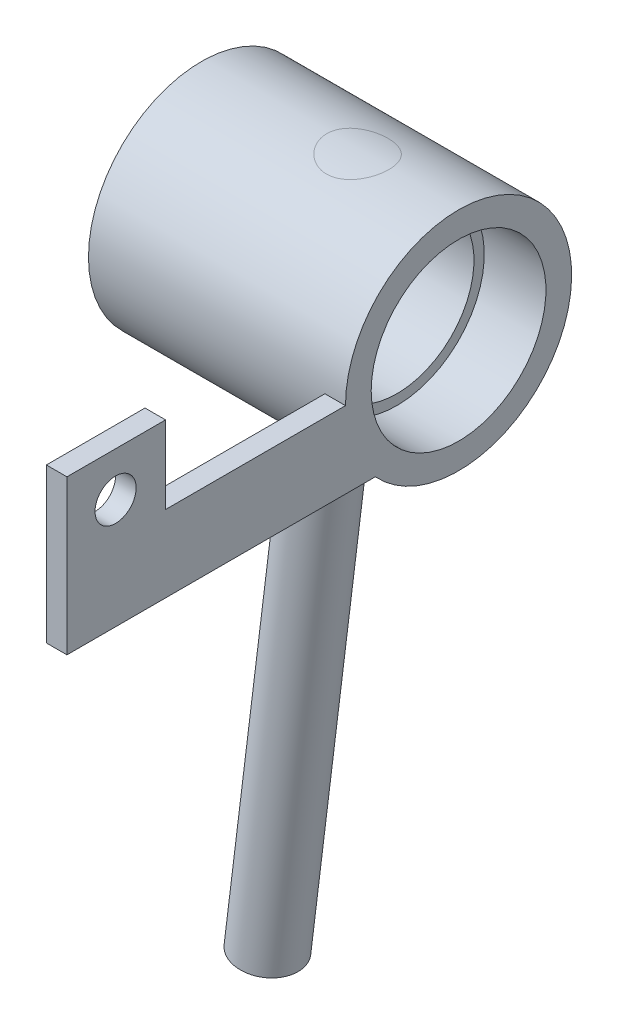
SolidWorks part; units mm, degrees
ref_plane "Front Plane" through (0, 0, 0) normal (0, 0, 1) x (1, 0, 0)
ref_plane "Top Plane" through (0, 0, 0) normal (0, 1, 0) x (1, 0, 0)
ref_plane "Right Plane" through (0, 0, 0) normal (1, 0, 0) x (0, 0, -1)
sketch "Sketch1" plane through (0, 0, 0) normal (0, 0, 1) x (1, 0, 0)
  line L0 (-25, 22) -> (-25, 17)
  line L1 (-25, 17) -> (-13, 17)
  line L2 (-13, 17) -> (-13, 15)
  line L3 (-13, 15) -> (13, 15)
  line L4 (13, 15) -> (13, 17)
  line L5 (13, 17) -> (25, 17)
  line L6 (25, 17) -> (25, 22)
  line L7 (-25, 22) -> (25, 22)
  line L8 (-45.7661, 0) -> (25, 0) construction
  line L9 (55, 0) -> (-55, 0) construction
  point P4 (0, 22)
  point P9 (0, 15)
  dimension "D1" = 50
  dimension "D2" = 5
  dimension "D3" = 2
  dimension "D4" = 12
  dimension "D5" = 22
revolve "Revolve1" add sketch "Sketch1" angle 360 about L8
sketch "Sketch6" plane through (0, 0, 0) normal (1, 0, 0) x (0, 0, -1)
  line L0 (-17.9634, -22) -> (15.1324, -22) construction
  circle A0 centre (0, 0) radius 22 construction
ref_plane "Plane2" through (-2.6611, -21.6733, 0) normal (0.1219, 0.9925, 0) x (0, 0, -1)
sketch "Sketch7" plane through (-2.6611, -21.6733, 0) normal (0.1219, 0.9925, 0) x (0, 0, -1)
  line L0 (-200017.9634, -2.6811) -> (200015.1324, -2.6811) construction
  line L2 (0, 55) -> (0, -55) construction
  circle A0 centre (0, -2.6811) radius 6
  dimension "D1" = 12
split line "Split Line2"
sketch3d "3DSketch1"
  spline S0 degree 3 poles (11.4476, 22, 0.4001) (11.4476, 22, -0.4001) (11.4063, 21.9891, -0.7927) (11.2456, 21.9477, -1.5639) (11.124, 21.9167, -1.9465) (10.8108, 21.8404, -2.6701) (10.6199, 21.7952, -3.0126) (10.2834, 21.7207, -3.4982) (10.1623, 21.6946, -3.6559) (9.9077, 21.6419, -3.9561) (9.7739, 21.6152, -4.0991) (9.3535, 21.535, -4.508) (9.047, 21.4813, -4.7544) (8.3859, 21.3804, -5.1894) (8.0395, 21.3344, -5.3728) (7.4963, 21.2759, -5.5986) (7.3113, 21.2581, -5.6655) (6.933, 21.2266, -5.7823) (6.7391, 21.2129, -5.8322) (6.1576, 21.1796, -5.9524) (5.7664, 21.1674, -5.9949) (4.977, 21.1648, -6.0042) (4.5752, 21.1747, -5.9696) (3.7998, 21.2152, -5.8241) (3.4225, 21.2456, -5.7139) (2.8725, 21.3038, -5.4911) (2.6916, 21.3254, -5.4069) (2.3434, 21.3712, -5.223) (2.1749, 21.3955, -5.1228) (1.8492, 21.4462, -4.9063) (1.6918, 21.4726, -4.79) (1.3882, 21.5266, -4.541) (1.2413, 21.5544, -4.4075) (0.8244, 21.6373, -3.9886) (0.5778, 21.6916, -3.6854) (0.1453, 21.7926, -3.0317) (-0.0415, 21.8395, -2.6776) (-0.3386, 21.9165, -1.9494) (-0.4513, 21.9472, -1.5729) (-0.5658, 21.9786, -0.989) (-0.5948, 21.9867, -0.7905) (-0.633, 21.9973, -0.3959) (-0.6425, 22, -0.1987) (-0.6426, 22, 0.3925) (-0.6049, 21.9894, 0.788) (-0.4522, 21.9474, 1.5698) (-0.3395, 21.9167, 1.9468) (-0.043, 21.8399, 2.6744) (0.1434, 21.7931, 3.0283) (0.5762, 21.692, 3.6833) (0.8224, 21.6377, 3.9863) (1.2376, 21.5551, 4.4041) (1.3846, 21.5273, 4.5378) (1.6889, 21.4731, 4.7877) (1.8463, 21.4467, 4.9042) (2.3345, 21.3707, 5.2291) (2.6808, 21.3242, 5.413) (3.418, 21.246, 5.7126) (3.7964, 21.2155, 5.8231) (4.3768, 21.1851, 5.9325) (4.5724, 21.1775, 5.9595) (4.9684, 21.1677, 5.9942) (5.1689, 21.1655, 6.0018) (5.7637, 21.1674, 5.9953) (6.1556, 21.1795, 5.9527) (6.7369, 21.2128, 5.8327) (6.9306, 21.2264, 5.783) (7.3096, 21.2579, 5.6661) (7.495, 21.2757, 5.599) (8.0392, 21.3344, 5.373) (8.3861, 21.3804, 5.1893) (9.048, 21.4814, 4.7537) (9.3536, 21.535, 4.5079) (9.7735, 21.6151, 4.0995) (9.9072, 21.6418, 3.9566) (10.1615, 21.6945, 3.6569) (10.2827, 21.7206, 3.4992) (10.6195, 21.7951, 3.0134) (10.8099, 21.8402, 2.6716) (11.1221, 21.9163, 1.9515) (11.2445, 21.9474, 1.5686) (11.4063, 21.9891, 0.7938) (11.4476, 22, 0.4001) (11.4476, 22, -0.4001) (11.4063, 21.9891, -0.7927) knots -0.03125 -0.03125 0 0 0.03125 0.03125 0.0625 0.0625 0.09375 0.09375 0.109375 0.109375 0.125 0.125 0.15625 0.15625 0.1875 0.1875 0.203125 0.203125 0.21875 0.21875 0.25 0.25 0.28125 0.28125 0.3125 0.3125 0.328125 0.328125 0.34375 0.34375 0.359375 0.359375 0.375 0.375 0.40625 0.40625 0.4375 0.4375 0.46875 0.46875 0.484375 0.484375 0.5 0.5 0.53125 0.53125 0.5625 0.5625 0.59375 0.59375 0.625 0.625 0.640625 0.640625 0.65625 0.65625 0.6875 0.6875 0.71875 0.71875 0.734375 0.734375 0.75 0.75 0.78125 0.78125 0.796875 0.796875 0.8125 0.8125 0.84375 0.84375 0.875 0.875 0.890625 0.890625 0.90625 0.90625 0.9375 0.9375 0.96875 0.96875 1 1 1.03125 1.03125 1.0625 only from (11.4476, 22, 0) to (11.4476, 22, 0) construction
  spline S1 degree 3 poles (11.4476, 22, 0.4001) (11.4476, 22, -0.4001) (11.4063, 21.9891, -0.7927) (11.2456, 21.9477, -1.5639) (11.124, 21.9167, -1.9465) (10.8108, 21.8404, -2.6701) (10.6199, 21.7952, -3.0126) (10.2834, 21.7207, -3.4982) (10.1623, 21.6946, -3.6559) (9.9077, 21.6419, -3.9561) (9.7739, 21.6152, -4.0991) (9.3535, 21.535, -4.508) (9.047, 21.4813, -4.7544) (8.3859, 21.3804, -5.1894) (8.0395, 21.3344, -5.3728) (7.4963, 21.2759, -5.5986) (7.3113, 21.2581, -5.6655) (6.933, 21.2266, -5.7823) (6.7391, 21.2129, -5.8322) (6.1576, 21.1796, -5.9524) (5.7664, 21.1674, -5.9949) (4.977, 21.1648, -6.0042) (4.5752, 21.1747, -5.9696) (3.7998, 21.2152, -5.8241) (3.4225, 21.2456, -5.7139) (2.8725, 21.3038, -5.4911) (2.6916, 21.3254, -5.4069) (2.3434, 21.3712, -5.223) (2.1749, 21.3955, -5.1228) (1.8492, 21.4462, -4.9063) (1.6918, 21.4726, -4.79) (1.3882, 21.5266, -4.541) (1.2413, 21.5544, -4.4075) (0.8244, 21.6373, -3.9886) (0.5778, 21.6916, -3.6854) (0.1453, 21.7926, -3.0317) (-0.0415, 21.8395, -2.6776) (-0.3386, 21.9165, -1.9494) (-0.4513, 21.9472, -1.5729) (-0.5658, 21.9786, -0.989) (-0.5948, 21.9867, -0.7905) (-0.633, 21.9973, -0.3959) (-0.6425, 22, -0.1987) (-0.6426, 22, 0.3925) (-0.6049, 21.9894, 0.788) (-0.4522, 21.9474, 1.5698) (-0.3395, 21.9167, 1.9468) (-0.043, 21.8399, 2.6744) (0.1434, 21.7931, 3.0283) (0.5762, 21.692, 3.6833) (0.8224, 21.6377, 3.9863) (1.2376, 21.5551, 4.4041) (1.3846, 21.5273, 4.5378) (1.6889, 21.4731, 4.7877) (1.8463, 21.4467, 4.9042) (2.3345, 21.3707, 5.2291) (2.6808, 21.3242, 5.413) (3.418, 21.246, 5.7126) (3.7964, 21.2155, 5.8231) (4.3768, 21.1851, 5.9325) (4.5724, 21.1775, 5.9595) (4.9684, 21.1677, 5.9942) (5.1689, 21.1655, 6.0018) (5.7637, 21.1674, 5.9953) (6.1556, 21.1795, 5.9527) (6.7369, 21.2128, 5.8327) (6.9306, 21.2264, 5.783) (7.3096, 21.2579, 5.6661) (7.495, 21.2757, 5.599) (8.0392, 21.3344, 5.373) (8.3861, 21.3804, 5.1893) (9.048, 21.4814, 4.7537) (9.3536, 21.535, 4.5079) (9.7735, 21.6151, 4.0995) (9.9072, 21.6418, 3.9566) (10.1615, 21.6945, 3.6569) (10.2827, 21.7206, 3.4992) (10.6195, 21.7951, 3.0134) (10.8099, 21.8402, 2.6716) (11.1221, 21.9163, 1.9515) (11.2445, 21.9474, 1.5686) (11.4063, 21.9891, 0.7938) (11.4476, 22, 0.4001) (11.4476, 22, -0.4001) (11.4063, 21.9891, -0.7927) knots -0.03125 -0.03125 0 0 0.03125 0.03125 0.0625 0.0625 0.09375 0.09375 0.109375 0.109375 0.125 0.125 0.15625 0.15625 0.1875 0.1875 0.203125 0.203125 0.21875 0.21875 0.25 0.25 0.28125 0.28125 0.3125 0.3125 0.328125 0.328125 0.34375 0.34375 0.359375 0.359375 0.375 0.375 0.40625 0.40625 0.4375 0.4375 0.46875 0.46875 0.484375 0.484375 0.5 0.5 0.53125 0.53125 0.5625 0.5625 0.59375 0.59375 0.625 0.625 0.640625 0.640625 0.65625 0.65625 0.6875 0.6875 0.71875 0.71875 0.734375 0.734375 0.75 0.75 0.78125 0.78125 0.796875 0.796875 0.8125 0.8125 0.84375 0.84375 0.875 0.875 0.890625 0.890625 0.90625 0.90625 0.9375 0.9375 0.96875 0.96875 1 1 1.03125 1.03125 1.0625 only from (11.4476, 22, 0) to (11.4476, 22, 0)
sketch3d "3DSketch2"
  spline S0 degree 3 poles (6.0451, -22, -0.3998) (6.0451, -22, 0.3998) (6.0065, -21.9891, 0.7928) (5.8933, -21.958, 1.3724) (5.8463, -21.9452, 1.5639) (5.733, -21.9148, 1.9437) (5.6666, -21.8972, 2.1321) (5.4429, -21.8392, 2.68) (5.2603, -21.7934, 3.0263) (4.8277, -21.6923, 3.6815) (4.576, -21.6369, 3.9908) (4.0249, -21.5273, 4.5446) (3.7233, -21.4727, 4.793) (3.0653, -21.3702, 5.231) (2.7159, -21.3236, 5.4154) (2.1711, -21.2658, 5.6367) (1.9855, -21.2484, 5.7016) (1.6063, -21.2182, 5.8131) (1.4116, -21.2053, 5.8599) (0.8265, -21.1747, 5.9699) (0.4338, -21.1649, 6.0038) (-0.3568, -21.1673, 5.9955) (-0.7573, -21.1797, 5.952) (-1.5298, -21.224, 5.7922) (-1.906, -21.2557, 5.6764) (-2.6383, -21.3345, 5.3725) (-2.9874, -21.381, 5.1868) (-3.4775, -21.4558, 4.8643) (-3.6358, -21.4817, 4.7491) (-3.9422, -21.5345, 4.5033) (-4.0909, -21.5617, 4.3719) (-4.5145, -21.6425, 3.9598) (-4.767, -21.6955, 3.662) (-5.1016, -21.7696, 3.18) (-5.2057, -21.7933, 3.0134) (-5.3984, -21.8383, 2.6679) (-5.4865, -21.8595, 2.4894) (-5.7211, -21.9167, 1.9474) (-5.8404, -21.9471, 1.5737) (-5.9622, -21.9784, 0.994) (-5.9933, -21.9865, 0.7963) (-6.0346, -21.9973, 0.4001) (-6.0449, -22, 0.2025) (-6.0454, -22.0001, -0.3891) (-6.0057, -21.9896, -0.7818) (-5.8436, -21.9479, -1.5637) (-5.7238, -21.9173, -1.9398) (-5.4124, -21.8414, -2.6619) (-5.218, -21.7954, -3.0115) (-4.7706, -21.6963, -3.6576) (-4.5178, -21.6432, -3.9561) (-4.0951, -21.5624, -4.3681) (-3.9463, -21.5353, -4.4998) (-3.6396, -21.4823, -4.7463) (-3.4813, -21.4564, -4.8616) (-2.9913, -21.3815, -5.1845) (-2.645, -21.3353, -5.3692) (-1.9106, -21.2561, -5.6749) (-1.5344, -21.2243, -5.7908) (-0.9571, -21.1911, -5.9108) (-0.7624, -21.1824, -5.9418) (-0.3686, -21.1703, -5.985) (-0.1682, -21.1668, -5.9972) (0.4278, -21.1648, -6.0043) (0.8203, -21.1745, -5.9704) (1.5955, -21.2147, -5.8259) (1.9817, -21.2458, -5.7132) (2.711, -21.323, -5.4179) (3.0577, -21.3692, -5.2353) (3.5509, -21.4458, -4.9081) (3.7108, -21.4726, -4.7899) (4.0144, -21.5267, -4.5409) (4.1592, -21.5541, -4.4094) (4.435, -21.6088, -4.1327) (4.566, -21.6362, -3.9875) (4.8143, -21.69, -3.6832) (4.9321, -21.7167, -3.5231) (5.2586, -21.793, -3.0295) (5.4414, -21.8389, -2.6829) (5.7392, -21.916, -1.9552) (5.8544, -21.9473, -1.5704) (6.0065, -21.9891, -0.7939) (6.0451, -22, -0.3998) (6.0451, -22, 0.3998) (6.0065, -21.9891, 0.7928) knots -0.03125 -0.03125 0 0 0.03125 0.03125 0.046875 0.046875 0.0625 0.0625 0.09375 0.09375 0.125 0.125 0.15625 0.15625 0.1875 0.1875 0.203125 0.203125 0.21875 0.21875 0.25 0.25 0.28125 0.28125 0.3125 0.3125 0.34375 0.34375 0.359375 0.359375 0.375 0.375 0.40625 0.40625 0.421875 0.421875 0.4375 0.4375 0.46875 0.46875 0.484375 0.484375 0.5 0.5 0.53125 0.53125 0.5625 0.5625 0.59375 0.59375 0.625 0.625 0.640625 0.640625 0.65625 0.65625 0.6875 0.6875 0.71875 0.71875 0.734375 0.734375 0.75 0.75 0.78125 0.78125 0.8125 0.8125 0.84375 0.84375 0.859375 0.859375 0.875 0.875 0.890625 0.890625 0.90625 0.90625 0.9375 0.9375 0.96875 0.96875 1 1 1.03125 1.03125 1.046875 only from (6.0451, -22, 0) to (6.0451, -22, 0) construction
  spline S1 degree 3 poles (6.0451, -22, -0.3998) (6.0451, -22, 0.3998) (6.0065, -21.9891, 0.7928) (5.8933, -21.958, 1.3724) (5.8463, -21.9452, 1.5639) (5.733, -21.9148, 1.9437) (5.6666, -21.8972, 2.1321) (5.4429, -21.8392, 2.68) (5.2603, -21.7934, 3.0263) (4.8277, -21.6923, 3.6815) (4.576, -21.6369, 3.9908) (4.0249, -21.5273, 4.5446) (3.7233, -21.4727, 4.793) (3.0653, -21.3702, 5.231) (2.7159, -21.3236, 5.4154) (2.1711, -21.2658, 5.6367) (1.9855, -21.2484, 5.7016) (1.6063, -21.2182, 5.8131) (1.4116, -21.2053, 5.8599) (0.8265, -21.1747, 5.9699) (0.4338, -21.1649, 6.0038) (-0.3568, -21.1673, 5.9955) (-0.7573, -21.1797, 5.952) (-1.5298, -21.224, 5.7922) (-1.906, -21.2557, 5.6764) (-2.6383, -21.3345, 5.3725) (-2.9874, -21.381, 5.1868) (-3.4775, -21.4558, 4.8643) (-3.6358, -21.4817, 4.7491) (-3.9422, -21.5345, 4.5033) (-4.0909, -21.5617, 4.3719) (-4.5145, -21.6425, 3.9598) (-4.767, -21.6955, 3.662) (-5.1016, -21.7696, 3.18) (-5.2057, -21.7933, 3.0134) (-5.3984, -21.8383, 2.6679) (-5.4865, -21.8595, 2.4894) (-5.7211, -21.9167, 1.9474) (-5.8404, -21.9471, 1.5737) (-5.9622, -21.9784, 0.994) (-5.9933, -21.9865, 0.7963) (-6.0346, -21.9973, 0.4001) (-6.0449, -22, 0.2025) (-6.0454, -22.0001, -0.3891) (-6.0057, -21.9896, -0.7818) (-5.8436, -21.9479, -1.5637) (-5.7238, -21.9173, -1.9398) (-5.4124, -21.8414, -2.6619) (-5.218, -21.7954, -3.0115) (-4.7706, -21.6963, -3.6576) (-4.5178, -21.6432, -3.9561) (-4.0951, -21.5624, -4.3681) (-3.9463, -21.5353, -4.4998) (-3.6396, -21.4823, -4.7463) (-3.4813, -21.4564, -4.8616) (-2.9913, -21.3815, -5.1845) (-2.645, -21.3353, -5.3692) (-1.9106, -21.2561, -5.6749) (-1.5344, -21.2243, -5.7908) (-0.9571, -21.1911, -5.9108) (-0.7624, -21.1824, -5.9418) (-0.3686, -21.1703, -5.985) (-0.1682, -21.1668, -5.9972) (0.4278, -21.1648, -6.0043) (0.8203, -21.1745, -5.9704) (1.5955, -21.2147, -5.8259) (1.9817, -21.2458, -5.7132) (2.711, -21.323, -5.4179) (3.0577, -21.3692, -5.2353) (3.5509, -21.4458, -4.9081) (3.7108, -21.4726, -4.7899) (4.0144, -21.5267, -4.5409) (4.1592, -21.5541, -4.4094) (4.435, -21.6088, -4.1327) (4.566, -21.6362, -3.9875) (4.8143, -21.69, -3.6832) (4.9321, -21.7167, -3.5231) (5.2586, -21.793, -3.0295) (5.4414, -21.8389, -2.6829) (5.7392, -21.916, -1.9552) (5.8544, -21.9473, -1.5704) (6.0065, -21.9891, -0.7939) (6.0451, -22, -0.3998) (6.0451, -22, 0.3998) (6.0065, -21.9891, 0.7928) knots -0.03125 -0.03125 0 0 0.03125 0.03125 0.046875 0.046875 0.0625 0.0625 0.09375 0.09375 0.125 0.125 0.15625 0.15625 0.1875 0.1875 0.203125 0.203125 0.21875 0.21875 0.25 0.25 0.28125 0.28125 0.3125 0.3125 0.34375 0.34375 0.359375 0.359375 0.375 0.375 0.40625 0.40625 0.421875 0.421875 0.4375 0.4375 0.46875 0.46875 0.484375 0.484375 0.5 0.5 0.53125 0.53125 0.5625 0.5625 0.59375 0.59375 0.625 0.625 0.640625 0.640625 0.65625 0.65625 0.6875 0.6875 0.71875 0.71875 0.734375 0.734375 0.75 0.75 0.78125 0.78125 0.8125 0.8125 0.84375 0.84375 0.859375 0.859375 0.875 0.875 0.890625 0.890625 0.90625 0.90625 0.9375 0.9375 0.96875 0.96875 1 1 1.03125 1.03125 1.046875 only from (6.0451, -22, 0) to (6.0451, -22, 0)
sketch "Sketch8" plane through (25, 0, 0) normal (1, 0, 0) x (0, 0, -1)
  line L0 (-22, 0) -> (-57, 0)
  line L2 (-76.1881, -14.8979) -> (-16.1881, -14.8979)
  line L4 (-76.1881, 15.1021) -> (-57, 15.1021)
  line L5 (-57, 15.1021) -> (-57, 0)
  line L6 (-76.1881, 15.1021) -> (-76.1881, -14.8979)
  circle A1 centre (0, 0) radius 22 construction
  arc A2 (-22, 0) -> (-16.1881, -14.8979) centre (0, 0) ccw
  circle A3 centre (-66.7249, 6.5179) radius 4
  point P11 (-20.4956, -7.9957)
  dimension "D5" = 8
  dimension "D1" = 60
  dimension "D2" = 30
  dimension "D3" = 15.1021
  dimension "D4" = 35
extrude "Boss-Extrude1" add sketch "Sketch8" against normal blind 4
extrude "Boss-Extrude2" add sketch "Sketch7<2>" along normal blind 7 and the other way blind 100 from offset 0 contours A0
sketch "Sketch7<2>" plane through (-2.6611, -21.6733, 0) normal (0.1219, 0.9925, 0) x (0, 0, -1) same geometry as "Sketch7"
